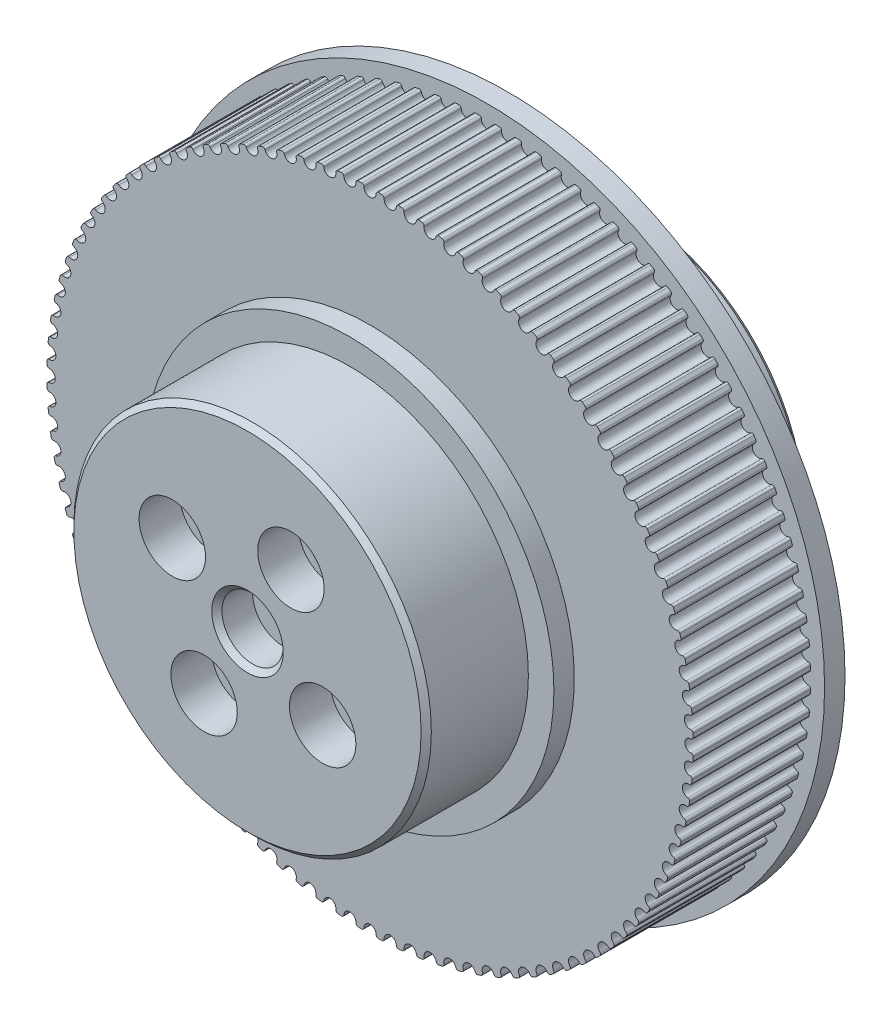
SolidWorks part; units mm, degrees
ref_plane "Спереди" through (0, 0, 0) normal (0, 0, 1) x (1, 0, 0)
ref_plane "Сверху" through (0, 0, 0) normal (0, 1, 0) x (1, 0, 0)
ref_plane "Справа" through (0, 0, 0) normal (1, 0, 0) x (0, 0, -1)
ref_axis "Ось1" through (0, 0, 55) along (0, 0, -1)
sketch "SketchRevolveGearBelt01" plane through (0, 0, 0) normal (1, 0, 0) x (0, 0, -1)
  line L0 (0, 0) -> (11.5, 0)
  line L1 (11.5, 0) -> (11.5, 31.6405)
  line L2 (11.5, 31.6405) -> (0, 31.6405)
  line L3 (0, 31.6405) -> (0, 0)
  dimension "GearBeltOutsideDiameter" = 31.6405
  dimension "D1" = 11.5
revolve "GearBelt01" add sketch "SketchRevolveGearBelt01" angle 360 about L0
sketch "SketchToothGearBelt01" plane through (0, 0, 0) normal (0, 0, 1) x (1, 0, 0)
  line L0 (-0.814, 31.63) -> (0, 34.1805)
  line L1 (0, 34.1805) -> (0.814, 31.63)
  arc A0 (0.814, 31.63) -> (0.6, 31.4215) centre (0.8086, 31.4215) ccw
  arc A1 (0.6, 31.4215) -> (-0.6, 31.4215) centre (0, 31.4215) cw
  arc A2 (-0.6, 31.4215) -> (-0.814, 31.63) centre (-0.8086, 31.4215) ccw
  dimension "GearBeltToothR1" = 0.4172
  dimension "GearBeltToothR2" = 1.2
  dimension "GearBeltToothCapX1" = 0.814
  dimension "GearBeltToothCapY1" = 2.5505
  dimension "GearBeltToothCapX2" = 0.814
  dimension "GearBeltToothCapY2" = 2.5505
extrude "ToothExtrudeCutGearBelt01" cut sketch "SketchToothGearBelt01" against normal blind 11.5
ref_axis "Ось2" through (34.8045, 0, 0) along (-1, 0, 0)
ref_plane "Плоскость1" through (0, 0, 0) normal (0, 0, -1) x (1, 0, 0)
pattern_circular "PatternGearBelt01" count 100 every 3.6 about axis through (0, 0, 55) along (0, 0, -1) of "ToothExtrudeCutGearBelt01"
sketch "Эскиз5" plane through (0, 0, 0) normal (0, 0, -1) x (-1, 0, 0)
  circle A0 centre (0, 0) radius 33
  dimension "D1" = 66
extrude "Бобышка-Вытянуть1" [suppressed] add sketch "Эскиз5" against normal blind 2
sketch "Эскиз20" plane through (0, 0, -11.5) normal (0, 0, -1) x (-1, 0, 0)
  circle A0 centre (0, 0) radius 33
  dimension "D1" = 66
extrude "Бобышка-Вытянуть10" add sketch "Эскиз20" along normal blind 2
sketch "Эскиз12" plane through (0, 0, -13.5) normal (0, 0, -1) x (-1, 0, 0)
  circle A0 centre (0, 0) radius 20
extrude "Бобышка-Вытянуть5" add sketch "Эскиз12" along normal blind 2
sketch "Эскиз6" plane through (0, 0, 0) normal (0, 0, 1) x (1, 0, 0)
  circle A0 centre (0, 0) radius 20
  dimension "D1" = 40
extrude "Бобышка-Вытянуть6" add sketch "Эскиз6" along normal blind 2
sketch "Эскиз13" plane through (0, 0, 2) normal (0, 0, 1) x (1, 0, 0)
  circle A0 centre (0, 0) radius 17.5
  dimension "D1" = 35
extrude "Бобышка-Вытянуть7" add sketch "Эскиз13" along normal blind 10
sketch "Эскиз14" plane through (0, 0, -15.5) normal (0, 0, -1) x (-1, 0, 0)
  circle A0 centre (0, 0) radius 17.5
  dimension "D1" = 35
extrude "Бобышка-Вытянуть8" add sketch "Эскиз14" along normal blind 10
sketch "Эскиз15" plane through (0, 0, -25.5) normal (0, 0, -1) x (-1, 0, 0)
  circle A0 centre (0, 0) radius 12.1
  dimension "D1" = 24.2
extrude "Вырез-Вытянуть1" cut sketch "Эскиз15" against normal blind 7
sketch "Эскиз16" plane through (0, 0, 0) normal (0, 0, 1) x (1, 0, 0)
  line L0 (0, 0) -> (4.25, 7.3612) construction
  line L1 (0, 0) -> (-46.2056, 0) construction
  line L2 (0, 0) -> (7.3612, -4.25) construction
  line L3 (0, 0) -> (-4.25, -7.3612) construction
  line L4 (0, 0) -> (-7.3612, 4.25) construction
  circle A0 centre (0, 0) radius 8.5 construction
  circle A1 centre (4.25, 7.3612) radius 1.75
  circle A2 centre (7.3612, -4.25) radius 1.75
  circle A3 centre (-4.25, -7.3612) radius 1.75
  circle A4 centre (-7.3612, 4.25) radius 1.75
  point P16 (0, 0)
  dimension "D1" = 17
  dimension "D3" = 3.5
  dimension "D2" = 60
  dimension "D4" = 4
extrude "Вырез-Вытянуть2" cut sketch "Эскиз16" against normal through all both and the other way through all
sketch "Эскиз17" plane through (0, 0, 12) normal (0, 0, 1) x (1, 0, 0)
  circle A0 centre (4.25, 7.3612) radius 3.25
  circle A1 centre (7.3612, -4.25) radius 3.25
  circle A2 centre (-4.25, -7.3612) radius 3.25
  circle A3 centre (-7.3612, 4.25) radius 3.25
  point P12 (0, 0)
  dimension "D1" = 4
extrude "Вырез-Вытянуть3" cut sketch "Эскиз17" against normal blind 4
sketch "Эскиз18" plane through (0, 0, 12) normal (0, 0, 1) x (1, 0, 0)
  circle A0 centre (0, 0) radius 3
extrude "Вырез-Вытянуть4" cut sketch "Эскиз18" against normal blind 3.5
sketch "Эскиз19" plane through (0, 0, 0) normal (0, 0, 1) x (1, 0, 0)
  circle A0 centre (0, 0) radius 1
extrude "Вырез-Вытянуть5" cut sketch "Эскиз19" against normal through all both and the other way through all
chamfer "Фаска1" distance 0.5 angle 45 3 edges at (-12.1, 0, -25.5) (-17.5, 0, -25.5) (17.5, 0, 12)
fillet "Скругление1" radius 0.4 1 edges at (-12.1, 0, -18.5)
chamfer "Фаска2" distance 0.5 angle 45 1 edges at (3, 0, 12)
chamfer "Фаска3" [suppressed] distance 0.5 angle 45
